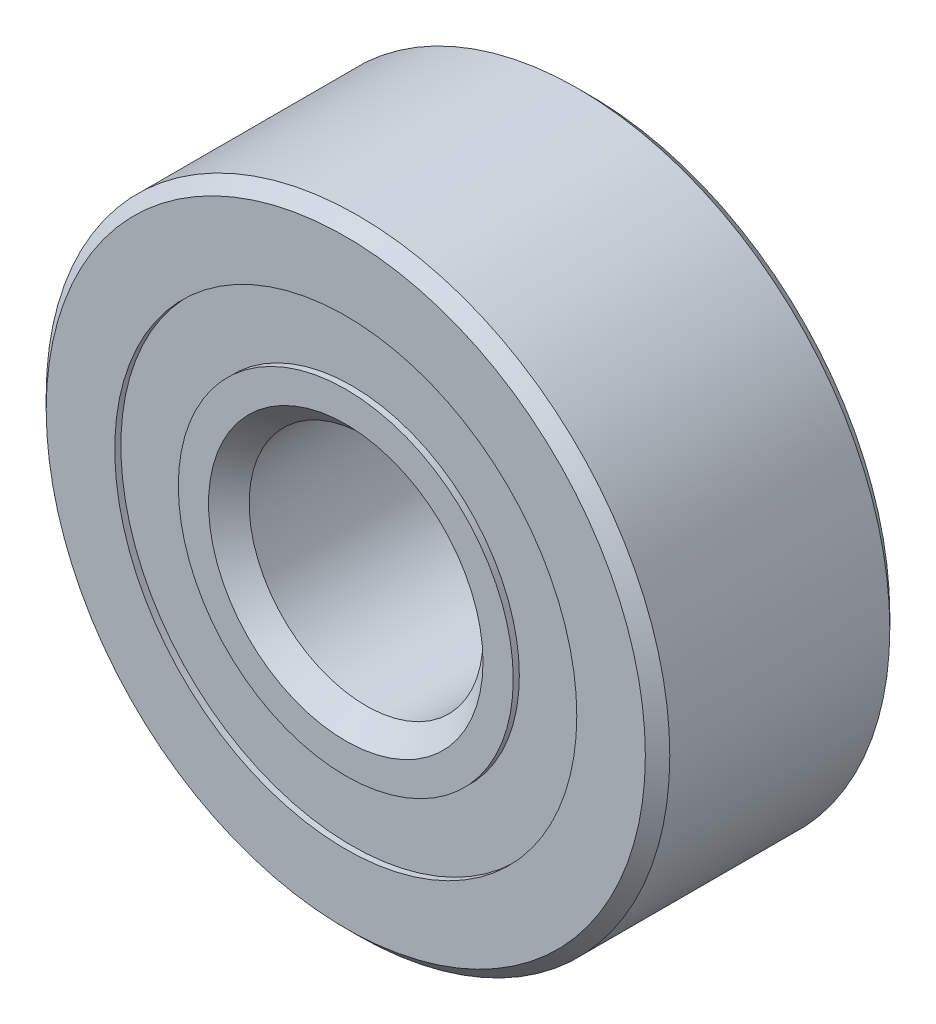
SolidWorks part; units mm, degrees
ref_plane "Front Plane" through (0, 0, 0) normal (0, 0, 1) x (1, 0, 0)
ref_plane "Top Plane" through (0, 0, 0) normal (0, 1, 0) x (1, 0, 0)
ref_plane "Right Plane" through (0, 0, 0) normal (1, 0, 0) x (0, 0, -1)
sketch "Sketch1" plane through (0, 0, 0) normal (1, 0, 0) x (0, 0, -1)
  line L0 (-2.4892, 0) -> (2.4892, 0) construction
  line L1 (0, 6.35) -> (0, -6.35) construction
  line L2 (2.2403, 6.35) -> (-2.2403, 6.35)
  line L3 (-2.2403, 6.35) -> (-2.4892, 6.1011)
  line L4 (-2.4892, 6.1011) -> (-2.4892, 4.705)
  line L5 (-2.4892, 4.705) -> (-1.1063, 4.705)
  line L6 (2.4892, 4.705) -> (1.1063, 4.705)
  line L7 (2.4892, 6.1011) -> (2.4892, 4.705)
  line L8 (2.2403, 6.35) -> (2.4892, 6.1011)
  line L9 (0, 6.35) -> (0, 4.3656) construction
  line L10 (0, 4.3656) -> (0, 2.3813) construction
  arc A0 (-1.1063, 4.705) -> (1.1063, 4.705) centre (0, 4.3656) cw
  point P14 (0, 2.3813)
  dimension "Width" = 4.9784
  dimension "OD" = 12.7
  dimension "D1" = 45
  dimension "D2" = 0.2489
  dimension "D3" = 2.2126
  dimension "D4" = 0.3394
revolve "Revolve1" add sketch "Sketch1" angle 360 about L0
sketch "Sketch2" plane through (0, 0, 0) normal (1, 0, 0) x (0, 0, -1)
  line L0 (-2.3647, 4.0262) -> (-1.1063, 4.0262)
  line L1 (-2.4892, 6.1011) -> (-2.4892, -6.1011) construction
  line L2 (-2.4892, 3.4105) -> (-2.3647, 3.4105) construction
  line L3 (-2.3647, 3.2861) -> (-1.8735, 2.7948)
  line L4 (-1.8735, 2.7948) -> (0, 2.7948)
  line L5 (0, 6.35) -> (0, -6.35) construction
  line L6 (0, 2.7948) -> (0, 3.2084)
  line L7 (0, 3.2084) -> (0, 2.3813) construction
  line L8 (-2.4892, 4.0262) -> (-2.4892, 2.7948) construction
  line L9 (-2.4892, 2.7948) -> (-1.8735, 2.7948) construction
  line L10 (-2.3647, 4.0262) -> (-2.3647, 3.2861)
  line L11 (-2.3647, 4.0262) -> (-2.3647, 6.2255) construction
  line L12 (-2.2403, 6.35) -> (-2.4892, 6.1011) construction
  arc A0 (-1.1063, 4.0262) -> (0, 3.2084) centre (0, 4.3656) ccw
  arc A1 (1.1063, 4.705) -> (-1.1063, 4.705) centre (0, 4.3656) ccw construction
  circle A2 centre (0, 4.3656) radius 1.1572 construction
  dimension "D1" = 45
revolve "Revolve2" [suppressed] add sketch "Sketch2" angle 360 about L0
sketch "Sketch3" plane through (0, 0, 0) normal (1, 0, 0) x (0, 0, -1)
  line L0 (-2.3647, 3.2861) -> (-1.8735, 2.7948)
  line L1 (-1.8735, 2.7948) -> (0, 2.7948)
  line L2 (0, 2.7948) -> (0, 3.2084)
  line L3 (-2.4892, 3.4105) -> (-2.4892, 2.7948)
  line L4 (-2.4892, 4.0262) -> (-2.4892, 2.7948) construction
  line L5 (-2.4892, 2.7948) -> (-2.0756, 2.3813)
  line L6 (-2.0756, 2.3813) -> (2.2403, 2.3812)
  line L7 (2.2403, 6.35) -> (2.2403, -6.35) construction
  line L8 (2.2403, 2.3812) -> (2.4892, 2.6302)
  line L9 (2.4892, -6.1011) -> (2.4892, 6.1011) construction
  line L10 (2.4892, 2.6302) -> (2.4892, 4.0262)
  line L11 (2.4892, 4.0262) -> (1.1063, 4.0262)
  line L12 (-2.4892, 3.4105) -> (-2.3647, 3.4105)
  line L13 (2.2403, 6.35) -> (2.4892, 6.1011) construction
  line L14 (-2.3647, 3.4105) -> (-2.3647, 3.2861)
  circle A0 centre (0, 4.3656) radius 1.1572 construction
  arc A1 (1.1063, 4.0262) -> (0, 3.2084) centre (0, 4.3656) cw
revolve "Revolve3" add sketch "Sketch3" angle 360 about L0
sketch "Sketch4" plane through (0, 0, 0) normal (1, 0, 0) x (0, 0, -1)
  line L0 (-1.1572, 4.3656) -> (1.1572, 4.3656)
  circle A1 centre (0, 4.3656) radius 1.1572 construction
  arc A2 (-1.1572, 4.3656) -> (1.1572, 4.3656) centre (0, 4.3656) cw
  arc A3 (1.1063, 4.705) -> (-1.1063, 4.705) centre (0, 4.3656) ccw construction
revolve "Revolve4" add sketch "Sketch4" angle 360 about L0
ref_axis "Axis1" through (0, 0, -2.4892) along (0, 0, 1)
pattern_circular "CirPattern1" count 8 every 45 about axis through (0, 0, -2.4892) along (0, 0, 1) of bodies 104
sketch "Sketch5" plane through (0, 0, 0) normal (1, 0, 0) x (0, 0, -1)
  line L0 (-2.4892, 4.705) -> (-1.1063, 4.705) construction
  line L1 (-2.3647, 4.705) -> (-1.1572, 4.705)
  line L2 (-2.3647, 4.705) -> (-2.3647, 3.4105)
  line L3 (-2.3647, 3.4105) -> (-1.1572, 3.4105)
  line L4 (-1.1572, 4.705) -> (-1.1572, 3.4105)
  line L6 (-2.2403, 6.35) -> (-2.4892, 6.1011) construction
  line L7 (0, 6.35) -> (0, 2.3813) construction
  line L8 (2.3647, 3.4105) -> (1.1572, 3.4105)
  line L9 (1.1572, 4.705) -> (1.1572, 3.4105)
  line L10 (2.3647, 4.705) -> (1.1572, 4.705)
  line L11 (2.3647, 4.705) -> (2.3647, 3.4105)
  circle A0 centre (0, 4.3656) radius 1.1572 construction
  point P10 (-2.3647, 6.2255)
revolve "Revolve5" add sketch "Sketch5" angle 360 about L0
equation "\"D2@Sketch1\" = \"Width@Sketch1\"*.05"
equation "\"D3@Sketch1\" = \"Width@Sketch1\"/2.25"
equation "\"D4@Sketch1\" = (((\"OD@Sketch1\"-\"Width@Sketch1\")/2)/3.25)/3.5"
equation "\"D2@CirPattern1\" = 360/\"Balls@CirPattern1\""
